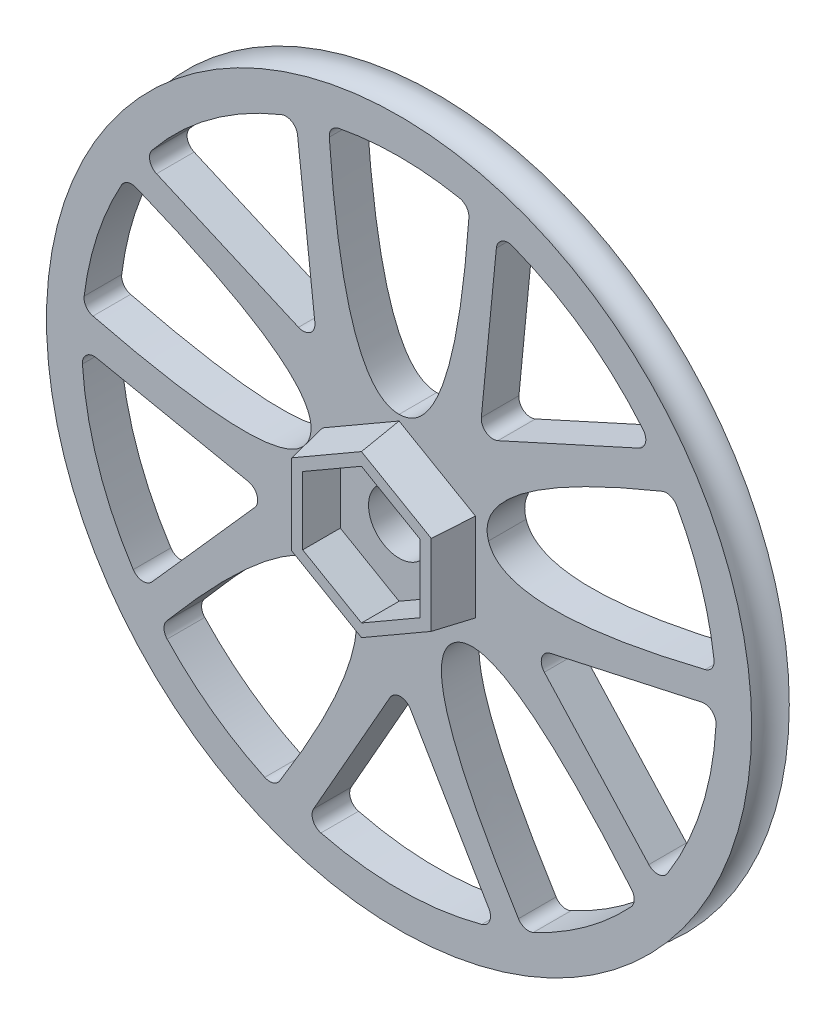
SolidWorks part; units mm, degrees
ref_plane "Front Plane" through (0, 0, 0) normal (0, 0, 1) x (1, 0, 0)
ref_plane "Top Plane" through (0, 0, 0) normal (0, 1, 0) x (1, 0, 0)
ref_plane "Right Plane" through (0, 0, 0) normal (1, 0, 0) x (0, 0, -1)
sketch "Sketch1" plane through (0, 0, 0) normal (0, 0, 1) x (1, 0, 0)
  circle A0 centre (0, 0) radius 38.1
  dimension "D1" = 76.2
extrude "Boss-Extrude1" add sketch "Sketch1" along normal mid plane 4.064
ref_axis "Axis1" through (0, 0, 17.7732) along (0, 0, -1)
sketch "Sketch2" plane through (0, 0, 0) normal (1, 0, 0) x (0, 0, -1)
  line L2 (-2.032, 38.1) -> (-2.032, -38.1) construction
  line L3 (-2.032, 38.1) -> (2.032, 38.1)
  circle A0 centre (0, 38.1) radius 2.032 construction
  arc A1 (-2.032, 38.1) -> (2.032, 38.1) centre (0, 38.1) ccw
revolve "Cut-Revolve1" cut sketch "Sketch2" angle 360 about axis through (0, 0, 17.7732) along (0, 0, -1)
sketch "Sketch3" plane through (0, 0, 0) normal (0, 0, 1) x (1, 0, 0)
  line L0 (0, 0) -> (0, 34.29) construction
  line L1 (0, 0) -> (34.29, 0) construction
  line L2 (-2.8815, 10.16) -> (2.8815, 10.16) construction
  line L3 (2.8814, 10.16) -> (-2.8815, 10.16) construction
  circle A0 centre (0, 0) radius 10.16 construction
  arc A1 (-7.62, 33.4326) -> (7.62, 33.4326) centre (0, 0) cw
  circle A2 centre (0, 0) radius 34.29 construction
  spline S0 degree 2 poles (0, 10.16) (6.0921, 10.16) (7.62, 33.4326) knots 0 0 0 1 1 1
  spline S1 degree 2 poles (0, 10.16) (-6.0921, 10.16) (-7.62, 33.4326) knots 0 0 0 1 1 1
  dimension "D1" = 20.32
  dimension "D2" = 68.58
  dimension "D3" = 15.24
extrude "Cut-Extrude1" cut sketch "Sketch3" against normal mid plane 5.08
pattern_circular "CirPattern1" count 5 over 360 about axis through (0, 0, 17.7732) along (0, 0, -1) of "Cut-Extrude1"
sketch "Sketch4" plane through (0, 0, 0) normal (0, 0, 1) x (1, 0, 0)
  line L0 (10.668, 32.5883) -> (8.6709, 12.1233)
  line L1 (8.6709, 12.1233) -> (27.3927, 20.6263)
  circle A0 centre (0, 0) radius 10.16 construction
  circle A1 centre (0, 0) radius 10.16 construction
  circle A2 centre (0, 0) radius 34.29 construction
  circle A3 centre (0, 0) radius 34.29 construction
  arc A4 (10.668, 32.5883) -> (27.3927, 20.6263) centre (0, 0) cw
  dimension "D1" = 3.048
  dimension "D2" = 3.048
  dimension "D3" = 60
extrude "Cut-Extrude2" cut sketch "Sketch4" against normal mid plane 5.08
pattern_circular "CirPattern2" count 5 over 360 about axis through (0, 0, 17.7732) along (0, 0, -1) of "Cut-Extrude2"
fillet "Fillet1" radius 1.27 25 edges at (-14.1408, -4.7113, 0) (0.1109, -14.9046, 0) (14.2094, -4.5003, 0) (8.6709, 12.1233, 0) (-8.8505, 11.9929, 0) (10.668, 32.5883, 0) (27.3927, 20.6263, 0) (34.151, 3.0842, 0) (29.4416, 17.5783, 0) (34.2899, -0.0755, 0) (28.0816, -19.6781, 0) (25.8159, -22.5686, 0) (13.4865, -31.5265, 0) (10.5243, -32.635, 0) (-10.0373, -32.788, 0) (-13.4865, -31.5265, 0) (-25.8159, -22.5686, 0) (-27.7855, -20.094, 0) (-34.285, -0.586, 0) (-34.151, 3.0842, 0) (-29.4416, 17.5783, 0) (-27.6967, 20.2162, 0) (-11.152, 32.4259, 0) (-7.62, 33.4326, 0) (7.62, 33.4326, 0)
sketch "Sketch5" plane through (0, 0, 2.032) normal (0, 0, 1) x (1, 0, 0)
  line L1 (-8.255, -4.766) -> (0, -9.5321)
  line L2 (0, -9.5321) -> (8.255, -4.766)
  line L3 (8.255, -4.766) -> (8.255, 4.766)
  line L4 (8.255, 4.766) -> (0, 9.5321)
  line L5 (0, 9.5321) -> (-8.255, 4.766)
  line L6 (-8.255, 4.766) -> (-8.255, -4.766)
  line L7 (0, 0) -> (0, 34.29) construction
  circle A0 centre (0, 0) radius 8.255 construction
  dimension "D1" = 16.51
extrude "Boss-Extrude2" add sketch "Sketch5" along normal blind 4.064 draft 10
sketch "Sketch6" plane through (0, 0, 6.096) normal (0, 0, 1) x (1, 0, 0)
  line L0 (0, 0) -> (0, 34.29) construction
  line L1 (0, -7.3323) -> (6.35, -3.6662)
  line L2 (6.35, -3.6662) -> (6.35, 3.6662)
  line L3 (6.35, 3.6662) -> (0, 7.3323)
  line L4 (0, 7.3323) -> (-6.35, 3.6662)
  line L5 (-6.35, 3.6662) -> (-6.35, -3.6662)
  line L6 (-6.35, -3.6662) -> (0, -7.3323)
  circle A0 centre (0, 0) radius 6.35 construction
  dimension "D1" = 12.7
extrude "Cut-Extrude3" cut sketch "Sketch6" against normal up to surface (4.064 mm away) up to face at (25.9693, -8.2247, 2.032)
sketch "Sketch7" plane through (0, 0, 2.032) normal (0, 0, 1) x (1, 0, 0)
  circle A0 centre (0, 0) radius 3.302
  dimension "D1" = 6.604
extrude "Cut-Extrude4" cut sketch "Sketch7" against normal up to next
